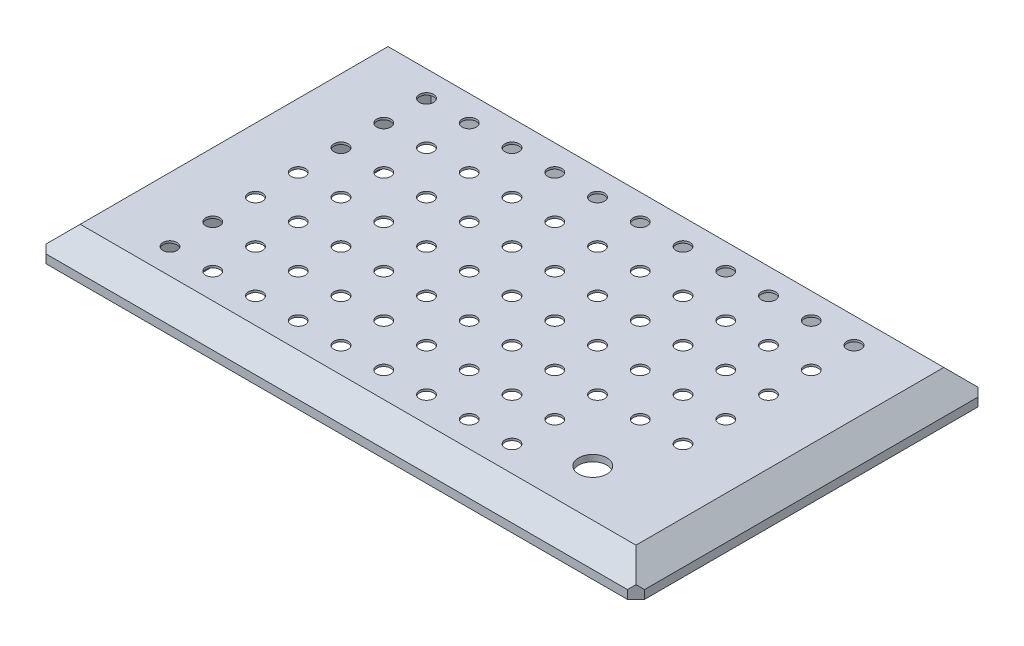
SolidWorks part; units mm, degrees
ref_plane "Front Plane" through (0, 0, 0) normal (0, 0, 1) x (1, 0, 0)
ref_plane "Top Plane" through (0, 0, 0) normal (0, 1, 0) x (1, 0, 0)
ref_plane "Right Plane" through (0, 0, 0) normal (1, 0, 0) x (0, 0, -1)
sketch "Sketch1" plane through (0, 0, 0) normal (0, 1, 0) x (1, 0, 0)
  line L1 (-70, -41) -> (70, -41)
  line L2 (-70, -41) -> (-70, 41)
  line L3 (-70, 41) -> (70, 41)
  line L4 (70, -41) -> (70, 41)
  line L5 (-70, -41) -> (70, 41) construction
  line L6 (-70, 41) -> (70, -41) construction
  point P0 (0, 0)
  dimension "D1" = 140
  dimension "D2" = 82
extrude "Boss-Extrude1" add sketch "Sketch1" along normal blind 2
sketch "Sketch2" plane through (0, 2, 0) normal (0, 1, 0) x (1, 0, 0)
  line L4 (70, -41) -> (70, 41)
  line L5 (70, 41) -> (-70, 41)
  line L6 (-70, 41) -> (-70, -41)
  line L7 (-70, -41) -> (70, -41)
  line L8 (70, -41) -> (70, 41)
  line L9 (70, 41) -> (-70, 41)
  line L10 (-70, 41) -> (-70, -41)
  line L11 (-70, -41) -> (70, -41)
  dimension "D1" = 0
ref_plane "Plane1" through (0, 7, 0) normal (0, 1, 0) x (1, 0, 0)
sketch "Sketch3" plane through (0, 7, 0) normal (0, 1, 0) x (1, 0, 0)
  line L0 (-70, 41) -> (-70, -41) construction
  line L1 (-65, -36) -> (65, -36)
  line L2 (-65, -36) -> (-65, 36)
  line L3 (-65, 36) -> (65, 36)
  line L4 (65, -36) -> (65, 36)
  line L5 (-65, -36) -> (65, 36) construction
  line L6 (-65, 36) -> (65, -36) construction
  line L7 (70, 41) -> (-70, 41) construction
  point P0 (0, 0)
  dimension "D1" = 5
  dimension "D2" = 5
loft "Loft1" add profiles "Sketch3", "Sketch2" connector at (-65, 7, 36) connector at (-70, 2, 41)
chamfer "Chamfer2" distance 2 angle 45 4 edges at (70, 1, 41) (70, 1, -41) (-70, 1, -41) (-70, 1, 41)
sketch "Sketch4" plane through (0, 0, 0) normal (0, -1, 0) x (1, 0, 0)
  line L0 (-70, -39) -> (-70, 39) construction
  line L1 (-62.9, 15) -> (-54.9, 15)
  line L2 (-62.9, 15) -> (-62.9, 25)
  line L3 (-62.9, 25) -> (-54.9, 25)
  line L4 (-54.9, 15) -> (-54.9, 25)
  line L5 (-62.9, 15) -> (-54.9, 25) construction
  line L6 (-62.9, 25) -> (-54.9, 15) construction
  line L7 (-70, 0) -> (70, 0) construction
  line L8 (70, 39) -> (70, -39) construction
  line L9 (0, 41) -> (0, -41) construction
  line L10 (-68, 41) -> (68, 41) construction
  line L11 (68, -41) -> (-68, -41) construction
  line L12 (-62.9, -25) -> (-54.9, -15) construction
  line L13 (-62.9, -15) -> (-54.9, -25) construction
  line L14 (-54.9, -15) -> (-54.9, -25)
  line L15 (-62.9, -25) -> (-54.9, -25)
  line L16 (-62.9, -15) -> (-62.9, -25)
  line L17 (-62.9, -15) -> (-54.9, -15)
  line L18 (62.9, -15) -> (54.9, -25) construction
  line L19 (62.9, -25) -> (54.9, -15) construction
  line L20 (62.9, 25) -> (54.9, 15) construction
  line L21 (62.9, 15) -> (54.9, 25) construction
  line L22 (62.9, -15) -> (54.9, -15)
  line L23 (62.9, -15) -> (62.9, -25)
  line L24 (62.9, -25) -> (54.9, -25)
  line L25 (54.9, -15) -> (54.9, -25)
  line L26 (54.9, 15) -> (54.9, 25)
  line L27 (62.9, 25) -> (54.9, 25)
  line L28 (62.9, 15) -> (62.9, 25)
  line L29 (62.9, 15) -> (54.9, 15)
  point P0 (-58.9, 20)
  point P21 (-58.9, -20)
  point P30 (58.9, -20)
  point P31 (58.9, 20)
  dimension "D1" = 10
  dimension "D2" = 7.1
  dimension "D3" = 8
  dimension "D4" = 40
extrude "Boss-Extrude2" add sketch "Sketch4" along normal blind 7
sketch "Sketch5" plane through (-62.9, 0, 0) normal (-1, 0, 0) x (0, 0, 1)
  line L0 (-15, 0) -> (-25, -7) construction
  line L1 (0, 0) -> (0, 50000) construction
  circle A0 centre (-20, -3.5) radius 2.05
  circle A1 centre (20, -3.5) radius 2.05
  dimension "D1" = 4.1
extrude "Cut-Extrude1" cut sketch "Sketch5" against normal through all
sketch "Sketch6" plane through (0, 0, 0) normal (0, -1, 0) x (1, 0, 0)
  line L0 (54.9, 25) -> (54.9, 15) construction
  line L1 (-53.9, -35) -> (53.9, -35)
  line L2 (-53.9, -35) -> (-53.9, 35)
  line L3 (-53.9, 35) -> (53.9, 35)
  line L4 (53.9, -35) -> (53.9, 35)
  line L5 (-53.9, -35) -> (53.9, 35) construction
  line L6 (-53.9, 35) -> (53.9, -35) construction
  line L8 (-65, 36) -> (65, 36) construction
  point P0 (0, 0)
  dimension "D1" = 1
  dimension "D2" = 1
extrude "Cut-Extrude2" cut sketch "Sketch6" against normal offset from surface (5.5 mm away) 1.5 up to face at (0, 7, 0)
sketch "Sketch7" plane through (0, 5.5, 0) normal (0, -1, 0) x (1, 0, 0)
  line L0 (0, 35) -> (0, -35) construction
  line L1 (-53.9, 35) -> (53.9, 35) construction
  line L2 (-53.9, -35) -> (53.9, -35) construction
  line L3 (-53.9, 0) -> (53.9, 0) construction
  line L4 (-53.9, -35) -> (-53.9, 35) construction
  line L5 (53.9, 35) -> (53.9, -35) construction
  circle A0 centre (0, 0) radius 1.65
  circle A1 centre (10, 0) radius 1.65
  circle A2 centre (20, 0) radius 1.65
  circle A3 centre (30, 0) radius 1.65
  circle A4 centre (40, 0) radius 1.65
  circle A5 centre (50, 0) radius 1.65
  circle A7 centre (10, 10) radius 1.65
  circle A8 centre (20, 10) radius 1.65
  circle A9 centre (30, 10) radius 1.65
  circle A10 centre (40, 10) radius 1.65
  circle A11 centre (50, 10) radius 1.65
  circle A13 centre (10, 20) radius 1.65
  circle A14 centre (20, 20) radius 1.65
  circle A15 centre (30, 20) radius 1.65
  circle A16 centre (40, 20) radius 1.65
  circle A17 centre (50, 20) radius 1.65
  circle A19 centre (10, 30) radius 1.65
  circle A20 centre (20, 30) radius 1.65
  circle A21 centre (30, 30) radius 1.65
  circle A22 centre (40, 30) radius 1.65
  circle A23 centre (50, 30) radius 1.65
  circle A25 centre (0, 10) radius 1.65
  circle A26 centre (0, 20) radius 1.65
  circle A27 centre (0, 30) radius 1.65
  circle A35 centre (-50, 30) radius 1.65
  circle A36 centre (-40, 30) radius 1.65
  circle A37 centre (-30, 30) radius 1.65
  circle A38 centre (-20, 30) radius 1.65
  circle A39 centre (-10, 30) radius 1.65
  circle A40 centre (-50, 20) radius 1.65
  circle A41 centre (-40, 20) radius 1.65
  circle A42 centre (-30, 20) radius 1.65
  circle A43 centre (-20, 20) radius 1.65
  circle A44 centre (-10, 20) radius 1.65
  circle A45 centre (-50, 10) radius 1.65
  circle A46 centre (-40, 10) radius 1.65
  circle A47 centre (-30, 10) radius 1.65
  circle A48 centre (-20, 10) radius 1.65
  circle A49 centre (-10, 10) radius 1.65
  circle A50 centre (-50, 0) radius 1.65
  circle A51 centre (-40, 0) radius 1.65
  circle A52 centre (-30, 0) radius 1.65
  circle A53 centre (-20, 0) radius 1.65
  circle A54 centre (-10, 0) radius 1.65
  circle A55 centre (-10, -10) radius 1.65
  circle A56 centre (-20, -10) radius 1.65
  circle A57 centre (-30, -10) radius 1.65
  circle A58 centre (-40, -10) radius 1.65
  circle A59 centre (-50, -10) radius 1.65
  circle A60 centre (-10, -20) radius 1.65
  circle A61 centre (-20, -20) radius 1.65
  circle A62 centre (-30, -20) radius 1.65
  circle A63 centre (-40, -20) radius 1.65
  circle A64 centre (-50, -20) radius 1.65
  circle A65 centre (-10, -30) radius 1.65
  circle A66 centre (-20, -30) radius 1.65
  circle A67 centre (-30, -30) radius 1.65
  circle A68 centre (-40, -30) radius 1.65
  circle A69 centre (-50, -30) radius 1.65
  circle A70 centre (0, -30) radius 1.65
  circle A71 centre (0, -20) radius 1.65
  circle A72 centre (0, -10) radius 1.65
  circle A73 centre (50, -30) radius 1.65
  circle A74 centre (40, -30) radius 1.65
  circle A75 centre (30, -30) radius 1.65
  circle A76 centre (20, -30) radius 1.65
  circle A77 centre (10, -30) radius 1.65
  circle A78 centre (50, -20) radius 1.65
  circle A79 centre (40, -20) radius 1.65
  circle A80 centre (30, -20) radius 1.65
  circle A81 centre (20, -20) radius 1.65
  circle A82 centre (10, -20) radius 1.65
  circle A83 centre (50, -10) radius 1.65
  circle A84 centre (40, -10) radius 1.65
  circle A85 centre (30, -10) radius 1.65
  circle A86 centre (20, -10) radius 1.65
  circle A87 centre (10, -10) radius 1.65
  dimension "D1" = 3.3
  dimension "D2" = 6
  dimension "D3" = 4
extrude "Cut-Extrude3" cut sketch "Sketch7" against normal through all
sketch "Sketch8" plane through (0, 5.5, 0) normal (0, -1, 0) x (1, 0, 0)
  line L0 (0, 35) -> (0, -35) construction
  line L1 (-53.9, 35) -> (53.9, 35) construction
  line L2 (53.9, -35) -> (-53.9, -35) construction
  line L3 (-53.9, 0) -> (53.9, 0) construction
  line L4 (-53.9, -35) -> (-53.9, 35) construction
  line L5 (53.9, -35) -> (53.9, 35) construction
  circle A0 centre (0, 0) radius 3.25
  circle A1 centre (10, 0) radius 3.25
  circle A2 centre (20, 0) radius 3.25
  circle A3 centre (30, 0) radius 3.25
  circle A4 centre (40, 0) radius 3.25
  circle A5 centre (50, 0) radius 3.25
  circle A6 centre (10, 10) radius 3.25
  circle A7 centre (20, 10) radius 3.25
  circle A8 centre (30, 10) radius 3.25
  circle A9 centre (40, 10) radius 3.25
  circle A10 centre (50, 10) radius 3.25
  circle A11 centre (10, 20) radius 3.25
  circle A12 centre (20, 20) radius 3.25
  circle A13 centre (30, 20) radius 3.25
  circle A14 centre (40, 20) radius 3.25
  circle A15 centre (50, 20) radius 3.25
  circle A16 centre (10, 30) radius 3.25
  circle A17 centre (20, 30) radius 3.25
  circle A18 centre (30, 30) radius 3.25
  circle A19 centre (40, 30) radius 3.25
  circle A20 centre (50, 30) radius 3.25
  circle A21 centre (0, 10) radius 3.25
  circle A22 centre (0, 20) radius 3.25
  circle A23 centre (0, 30) radius 3.25
  circle A24 centre (0, -30) radius 3.25
  circle A25 centre (0, -20) radius 3.25
  circle A26 centre (0, -10) radius 3.25
  circle A27 centre (50, -30) radius 3.25
  circle A28 centre (40, -30) radius 3.25
  circle A29 centre (30, -30) radius 3.25
  circle A30 centre (20, -30) radius 3.25
  circle A31 centre (10, -30) radius 3.25
  circle A32 centre (50, -20) radius 3.25
  circle A33 centre (40, -20) radius 3.25
  circle A34 centre (30, -20) radius 3.25
  circle A35 centre (20, -20) radius 3.25
  circle A36 centre (10, -20) radius 3.25
  circle A37 centre (50, -10) radius 3.25
  circle A38 centre (40, -10) radius 3.25
  circle A39 centre (30, -10) radius 3.25
  circle A40 centre (20, -10) radius 3.25
  circle A41 centre (10, -10) radius 3.25
  circle A42 centre (-10, -10) radius 3.25
  circle A43 centre (-20, -10) radius 3.25
  circle A44 centre (-30, -10) radius 3.25
  circle A45 centre (-40, -10) radius 3.25
  circle A46 centre (-50, -10) radius 3.25
  circle A47 centre (-10, -20) radius 3.25
  circle A48 centre (-20, -20) radius 3.25
  circle A49 centre (-30, -20) radius 3.25
  circle A50 centre (-40, -20) radius 3.25
  circle A51 centre (-50, -20) radius 3.25
  circle A52 centre (-10, -30) radius 3.25
  circle A53 centre (-20, -30) radius 3.25
  circle A54 centre (-30, -30) radius 3.25
  circle A55 centre (-40, -30) radius 3.25
  circle A56 centre (-50, -30) radius 3.25
  circle A57 centre (-50, 30) radius 3.25
  circle A58 centre (-40, 30) radius 3.25
  circle A59 centre (-30, 30) radius 3.25
  circle A60 centre (-20, 30) radius 3.25
  circle A61 centre (-10, 30) radius 3.25
  circle A62 centre (-50, 20) radius 3.25
  circle A63 centre (-40, 20) radius 3.25
  circle A64 centre (-30, 20) radius 3.25
  circle A65 centre (-20, 20) radius 3.25
  circle A66 centre (-10, 20) radius 3.25
  circle A67 centre (-50, 10) radius 3.25
  circle A68 centre (-40, 10) radius 3.25
  circle A69 centre (-30, 10) radius 3.25
  circle A70 centre (-20, 10) radius 3.25
  circle A71 centre (-10, 10) radius 3.25
  circle A72 centre (-50, 0) radius 3.25
  circle A73 centre (-40, 0) radius 3.25
  circle A74 centre (-30, 0) radius 3.25
  circle A75 centre (-20, 0) radius 3.25
  circle A76 centre (-10, 0) radius 3.25
  dimension "D1" = 6.5
  dimension "D2" = 6
  dimension "D3" = 4
extrude "Cut-Extrude4" cut sketch "Sketch8" against normal blind 1
sketch "Sketch9" plane through (0, 7, 0) normal (0, 1, 0) x (1, 0, 0)
  line L1 (53.9, -35) -> (33.9, -35)
  line L2 (53.9, -35) -> (53.9, -15)
  line L3 (53.9, -15) -> (33.9, -15)
  line L4 (33.9, -35) -> (33.9, -15)
  dimension "D1" = 20
  dimension "D2" = 20
extrude "Boss-Extrude3" add sketch "Sketch9" against normal up to surface (1.5 mm away) up to face at (10, 5.5, -6.75)
sketch "Sketch10" plane through (0, 5.5, 0) normal (0, -1, 0) x (1, 0, 0)
  line L1 (53.9, 35) -> (43.9, 35) construction
  line L2 (53.9, 35) -> (53.9, 25) construction
  line L3 (53.9, 25) -> (43.9, 25) construction
  line L4 (43.9, 35) -> (43.9, 25) construction
  circle A0 centre (43.9, 25) radius 3.3
  dimension "D1" = 6.6
  dimension "D2" = 10
extrude "Cut-Extrude5" cut sketch "Sketch10" against normal through all
sketch "Sketch11" plane through (0, 0, 0) normal (0, -1, 0) x (1, 0, 0)
  line L0 (53.9, 35) -> (53.9, -35) construction
  line L1 (53.9, 10) -> (63.9, 10)
  line L2 (53.9, 10) -> (53.9, -10)
  line L3 (53.9, -10) -> (63.9, -10)
  line L4 (63.9, 10) -> (63.9, -10)
  line L5 (-53.9, 35) -> (-53.9, -35) construction
  line L6 (-53.9, 10) -> (-63.9, 10)
  line L7 (-53.9, 10) -> (-53.9, -10)
  line L8 (-53.9, -10) -> (-63.9, -10)
  line L9 (-63.9, 10) -> (-63.9, -10)
  line L10 (-70, -39) -> (-70, 39) construction
  point P12 (-63.9, 0)
  point P15 (-70, 0)
  point P16 (63.9, 0)
  dimension "D1" = 10
  dimension "D2" = 20
extrude "Cut-Extrude6" cut sketch "Sketch11" against normal up to surface (5.5 mm away) up to face at (43.9, 5.5, 21.7)
